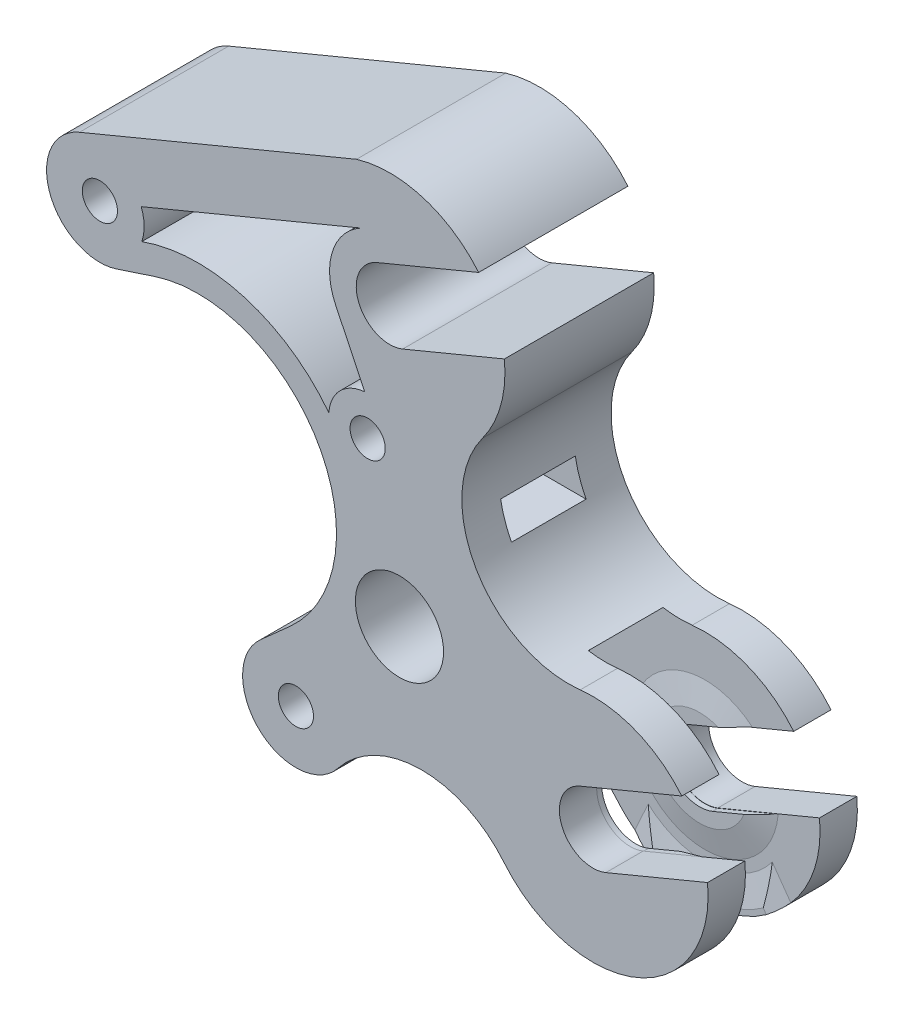
SolidWorks part; units mm, degrees
ref_plane "Front Plane" through (0, 0, 0) normal (0, 0, 1) x (1, 0, 0)
ref_plane "Top Plane" through (0, 0, 0) normal (0, 1, 0) x (1, 0, 0)
ref_plane "Right Plane" through (0, 0, 0) normal (1, 0, 0) x (0, 0, -1)
ref_plane "Plane1" through (0, 0, 7) normal (0, 0, 1) x (1, 0, 0)
sketch "Sketch1" plane through (0, 0, 0) normal (0, 0, 1) x (1, 0, 0)
  line L0 (18, 21) -> (37.0525, -11.9999) construction
  line L1 (15.9217, 9.1924) -> (-9.1924, 15.9217) construction
  line L2 (-9.1924, 15.9217) -> (-15.9217, -9.1924) construction
  line L3 (-15.9217, -9.1924) -> (9.1924, -15.9217) construction
  line L4 (9.1924, -15.9217) -> (15.9217, 9.1924) construction
  line L5 (0, 0) -> (50.7667, 0) construction
  line L6 (0, 0) -> (-9.1924, 15.9217) construction
  line L7 (-4.0727, 12.3456) -> (-7.626, 11.1734)
  line L8 (8.6552, -9.6998) -> (5.8634, -12.191)
  line L9 (0, 0) -> (9.1924, -15.9217) construction
  line L10 (14.8777, 31.3388) -> (-11.1111, 20.5389)
  line L11 (16.7912, 23.9088) -> (26.3307, 27.8731)
  line L12 (19.2088, 18.0912) -> (28.7483, 22.0554)
  line L13 (35.8437, -9.0911) -> (45.3832, -5.1268)
  line L14 (38.2613, -14.9087) -> (47.8008, -10.9445)
  arc A0 (8.6552, -9.6998) -> (-4.0727, 12.3456) centre (0, 0) ccw
  arc A1 (16.7912, 23.9088) -> (19.2088, 18.0912) centre (18, 21) ccw
  circle A2 centre (-9.1924, 15.9217) radius 1.65
  circle A3 centre (15.9217, 9.1924) radius 1.65
  circle A4 centre (9.1924, -15.9217) radius 1.65
  arc A5 (26.6989, 14.5993) -> (28.7483, 22.0554) centre (18, 21) ccw
  arc A6 (35.8437, -9.0911) -> (38.2613, -14.9087) centre (37.0525, -11.9999) ccw
  arc A7 (-11.1111, 20.5389) -> (-7.626, 11.1734) centre (-9.1924, 15.9217) ccw
  arc A8 (45.3832, -5.1268) -> (35.8587, -1.2661) centre (37.0525, -11.9999) ccw
  arc A9 (28.7062, -18.854) -> (47.8008, -10.9445) centre (37.0525, -11.9999) ccw
  arc A10 (5.8634, -12.191) -> (13.121, -19.0146) centre (9.1924, -15.9217) ccw
  arc A11 (28.7062, -18.854) -> (13.121, -19.0146) centre (20.9781, -25.2005) ccw
  arc A12 (26.6989, 14.5993) -> (35.8587, -1.2661) centre (34.7534, 8.6726) ccw
  arc A13 (26.3307, 27.8731) -> (14.8777, 31.3388) centre (18, 21) ccw
  dimension "D1" = 26
  dimension "D2" = 3.3
  dimension "D3" = 6.3
  dimension "D9" = 5
  dimension "D10" = 10.8
  dimension "D11" = 10
  dimension "D12" = 10
  dimension "D4" = 21
  dimension "D5" = 38.105
  dimension "D6" = 60
  dimension "D7" = 18
  dimension "D8" = 15
extrude "Boss-Extrude1" add sketch "Sketch1" along normal blind 14
sketch "Sketch3" plane through (0, 0, 7) normal (0, 0, 1) x (1, 0, 0)
  line L0 (0, 7) -> (37.0525, 7)
  line L1 (-2.9117, -6.3657) -> (32.2689, -22.4578)
  line L2 (5.7446, 4) -> (37.0525, 4)
  line L3 (3.5601, -6.0271) -> (26.4728, -16.5076)
  line L4 (37.0525, 4) -> (37.0525, 7)
  line L5 (0, 4) -> (23.3288, 4) construction
  line L6 (-1.6639, -3.6375) -> (33.5168, -19.7296) construction
  line L7 (0, 7) -> (23.3288, 7) construction
  circle A0 centre (37.0525, -11.9999) radius 9.5 construction
  arc A1 (32.2689, -22.4578) -> (26.4728, -16.5076) centre (37.0525, -11.9999) ccw
  arc A2 (35.8437, -9.0911) -> (38.2613, -14.9087) centre (37.0525, -11.9999) ccw construction
  circle A3 centre (0, 0) radius 5 construction
  arc A4 (0, 7) -> (-2.9117, -6.3657) centre (0, 0) ccw
  arc A6 (3.5601, -6.0271) -> (5.7446, 4) centre (0, 0) ccw
  dimension "D1" = 19
  dimension "D2" = 2
  dimension "D3" = 10
  dimension "D4" = 2
  dimension "D5" = 3
  dimension "D6" = 3
extrude "Cut-Extrude1" cut sketch "Sketch3" against normal blind 3.5 and the other way blind 3.5
sketch "Sketch4" plane through (0, 0, 14) normal (0, 0, 1) x (1, 0, 0)
  line L0 (15.6386, 12.8314) -> (12.9012, 18.566)
  line L1 (14.8777, 31.3388) -> (-11.1111, 20.5389) construction
  line L5 (15.2925, 25.959) -> (-5.3131, 17.3961)
  circle A0 centre (18.906, -4.6018) radius 4.1348
  arc A1 (12.2812, 9.4563) -> (-5.2659, 14.5781) centre (0, 0) ccw
  arc A2 (15.6386, 12.8314) -> (12.2812, 9.4563) centre (15.9217, 9.1924) ccw
  arc A3 (15.2925, 25.959) -> (12.9012, 18.566) centre (18, 21) ccw
  arc A4 (-5.2659, 14.5781) -> (-5.3131, 17.3961) centre (-9.1924, 15.9217) ccw
  arc A5 (16.7912, 23.9088) -> (19.2088, 18.0912) centre (18, 21) ccw construction
  arc A6 (8.6552, -9.6998) -> (-4.0727, 12.3456) centre (0, 0) ccw construction
  circle A7 centre (15.9217, 9.1924) radius 1.65 construction
  circle A8 centre (-9.1924, 15.9217) radius 1.65 construction
  dimension "D1" = 2.5
  dimension "D2" = 2.5
  dimension "D3" = 2
  dimension "D4" = 2.5
extrude "Cut-Extrude2" cut sketch "Sketch4" against normal through all
sketch "Sketch5" plane through (0, 0, 3.5) normal (0, 0, 1) x (1, 0, 0)
  line L0 (35.8356, -9.0715) -> (38.7839, -7.8463)
  line L1 (38.2694, -14.9283) -> (41.2177, -13.7031)
  line L2 (47.8008, -10.9445) -> (38.2613, -14.9087) construction
  line L3 (35.8437, -9.0911) -> (45.3832, -5.1268) construction
  line L4 (32.7681, -21.3665) -> (32.5601, -21.8212)
  line L5 (43.022, -20.3936) -> (43.3118, -20.8011)
  line L6 (26.4728, -16.5076) -> (9.5846, -8.7827) construction
  line L7 (37.0525, -11.9999) -> (43.022, -20.3936) construction
  line L8 (37.0525, -11.9999) -> (32.7681, -21.3665) construction
  arc A0 (35.8356, -9.0715) -> (38.2694, -14.9283) centre (37.0525, -11.9999) ccw
  arc A1 (38.7839, -7.8463) -> (41.2177, -13.7031) centre (37.0525, -11.9999) ccw
  arc A2 (28.7062, -18.854) -> (47.8008, -10.9445) centre (37.0525, -11.9999) ccw construction
  arc A3 (32.5601, -21.8212) -> (43.3118, -20.8011) centre (37.0525, -11.9999) ccw
  arc A4 (32.7681, -21.3665) -> (43.022, -20.3936) centre (37.0525, -11.9999) ccw
  dimension "D1" = 4.5
  dimension "D3" = 10.3
  dimension "D2" = 60
extrude "Boss-Extrude2" add sketch "Sketch5" along normal blind 0.5
chamfer "Chamfer1" distance 2.4 distance2 0.5 1 edges at (32.897, -13.7268, 3.5) first distance on face at (30.142, -12.9158, 3.5)
chamfer "Chamfer2" distance 2.4 distance2 0.5 3 edges at (32.6641, -21.5939, 3.5) (43.1669, -20.5974, 3.5) (38.0254, -22.2538, 3.5) first distance on face at (30.142, -12.9158, 3.5)
mirror "Mirror2" about plane through (0, 0, 7) normal (0, 0, 1) of "Boss-Extrude2"
chamfer "Chamfer3" distance 0.5 distance2 2.4 1 edges at (32.897, -13.7268, 10.5) first distance on face at (36.4489, -12.2507, 10.25)
chamfer "Chamfer4" distance 0.5 distance2 2.4 3 edges at (32.6641, -21.5939, 10.5) (38.0254, -22.2538, 10.5) (43.1669, -20.5974, 10.5) first distance on face at (32.6641, -21.5939, 10.25) first distance on face at (37.9602, -21.567, 10.25) first distance on face at (43.1669, -20.5974, 10.25)
